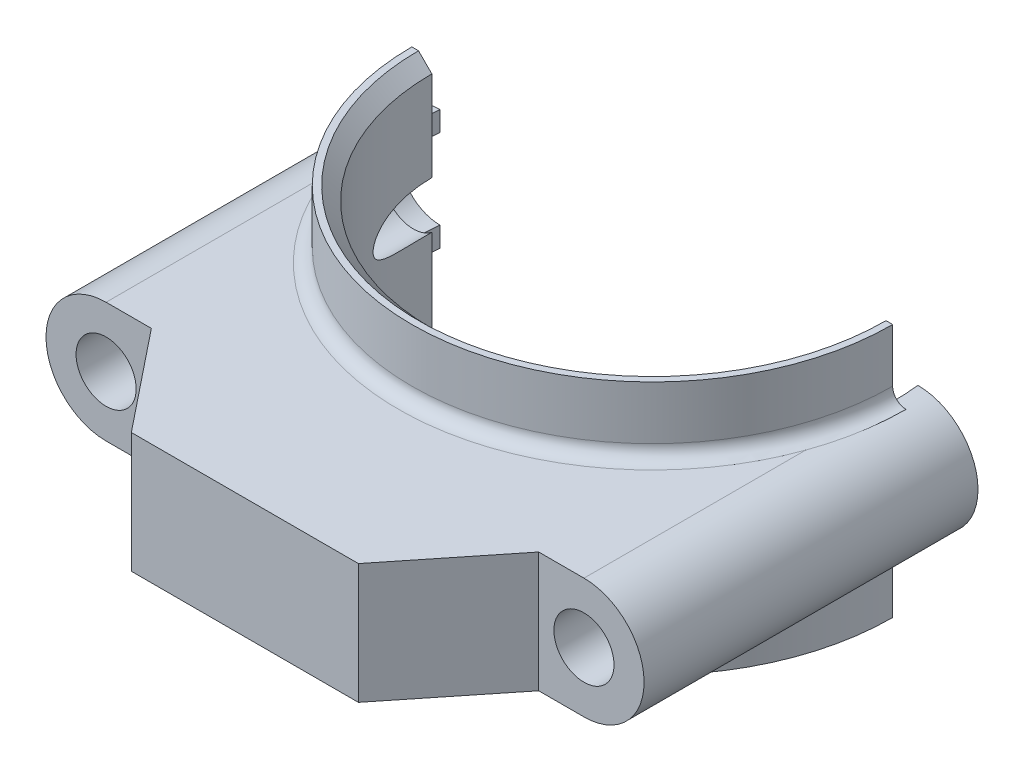
SolidWorks part; units mm, degrees
ref_plane "Front Plane" through (0, 0, 0) normal (0, 0, 1) x (1, 0, 0)
ref_plane "Top Plane" through (0, 0, 0) normal (0, 1, 0) x (1, 0, 0)
ref_plane "Right Plane" through (0, 0, 0) normal (1, 0, 0) x (0, 0, -1)
sketch "Sketch1" plane through (0, 0, 0) normal (0, 1, 0) x (1, 0, 0)
  line L0 (17, -61) -> (-17, -61)
  line L1 (35.7771, 4) -> (32.7567, 4)
  line L2 (0, 0) -> (-44.7771, 0) construction
  line L3 (-32.7567, 4) -> (-44.7771, 4)
  line L4 (0, 0) -> (0, -123.3824) construction
  line L5 (17, -61) -> (29, -46)
  line L6 (-44.7771, 4) -> (-44.7771, -46)
  line L7 (-17, -61) -> (-29, -46)
  line L8 (-29, -46) -> (-44.7771, -46)
  line L9 (29, -46) -> (44.7771, -46)
  line L10 (44.7771, 4) -> (44.7771, -46)
  line L11 (32.7567, 4) -> (44.7771, 4)
  arc A0 (-32.7567, 4) -> (32.7567, 4) centre (0, 0) ccw
  arc A1 (-35.7771, 4) -> (35.7771, 4) centre (0, 0) ccw
  point P7 (0, -61)
  point P9 (0, -61)
  point P10 (0, 4)
  point P18 (0, -46)
  dimension "D1" = 4
  dimension "D2" = 66
  dimension "D3" = 72
  dimension "D4" = 65
  dimension "D7" = 9
  dimension "D8" = 29
extrude "Boss-Extrude2" add sketch "Sketch1" along normal mid plane 18 contours A1 L3 L6 L8 L7 L0 L5 L9 L10 L11 region at (0, 0, 59.8934)
sketch "Sketch3" plane through (0, 0, 0) normal (0, 1, 0) x (1, 0, 0)
  line L2 (36, 0) -> (33, 0)
  line L3 (-33, 0) -> (-36, 0)
  arc A0 (-36, 0) -> (36, 0) centre (0, 0) ccw
  arc A1 (-33, 0) -> (33, 0) centre (0, 0) ccw
  point P11 (0, 0)
extrude "Boss-Extrude3" add sketch "Sketch3" along normal mid plane 38
chamfer "Chamfer1" distance 2 angle 45 2 edges at (0, -19, 33) (0, 19, 33)
sketch "Sketch5" plane through (0, 0, -4) normal (0, 0, -1) x (-1, 0, 0)
  line L1 (-35.7771, 9) -> (-44.7771, 9)
  line L2 (-44.7771, 9) -> (-44.7771, -9)
  line L3 (-44.7771, -9) -> (-35.7771, -9)
  arc A0 (-35.7771, 9) -> (-35.7771, -9) centre (-35.7771, 0) ccw
  line M1 (-44.7771, -9) -> (-35.7771, -9)
  line M3 (-35.7771, 9) -> (-44.7771, 9)
  line M4 (-44.7771, 9) -> (-44.7771, -9)
extrude "Cut-Extrude1" cut sketch "Sketch5" against normal blind 50 contours A0 M3 M4 | A0 L2 M1 region at (42.7668, 6.9897, -4) region at (42.7668, -6.9897, -4)
sketch "Sketch6" plane through (0, 0, -4) normal (0, 0, -1) x (-1, 0, 0)
  circle A0 centre (-35.7771, 0) radius 4.5
extrude "Cut-Extrude2" cut sketch "Sketch6" against normal blind 50
sketch "Sketch7" plane through (0, 0, -4) normal (0, 0, -1) x (-1, 0, 0)
  line L0 (-35.7771, 6) -> (-35.7771, 4.5)
  line L1 (-35.7771, -4.5) -> (-35.7771, -6)
  arc A0 (-35.7771, 4.5) -> (-35.7771, -4.5) centre (-35.7771, 0) ccw
  arc A1 (-35.7771, 6) -> (-35.7771, -6) centre (-35.7771, 0) ccw
extrude "Cut-Extrude3" cut sketch "Sketch7" against normal blind 4
mirror "Mirror2" about plane through (0, 0, 0) normal (1, 0, 0) of "Cut-Extrude2", "Cut-Extrude3", "Cut-Extrude1"
fillet "Fillet1" radius 2 2 edges at (0, -9, 36) (0, 9, 36)
